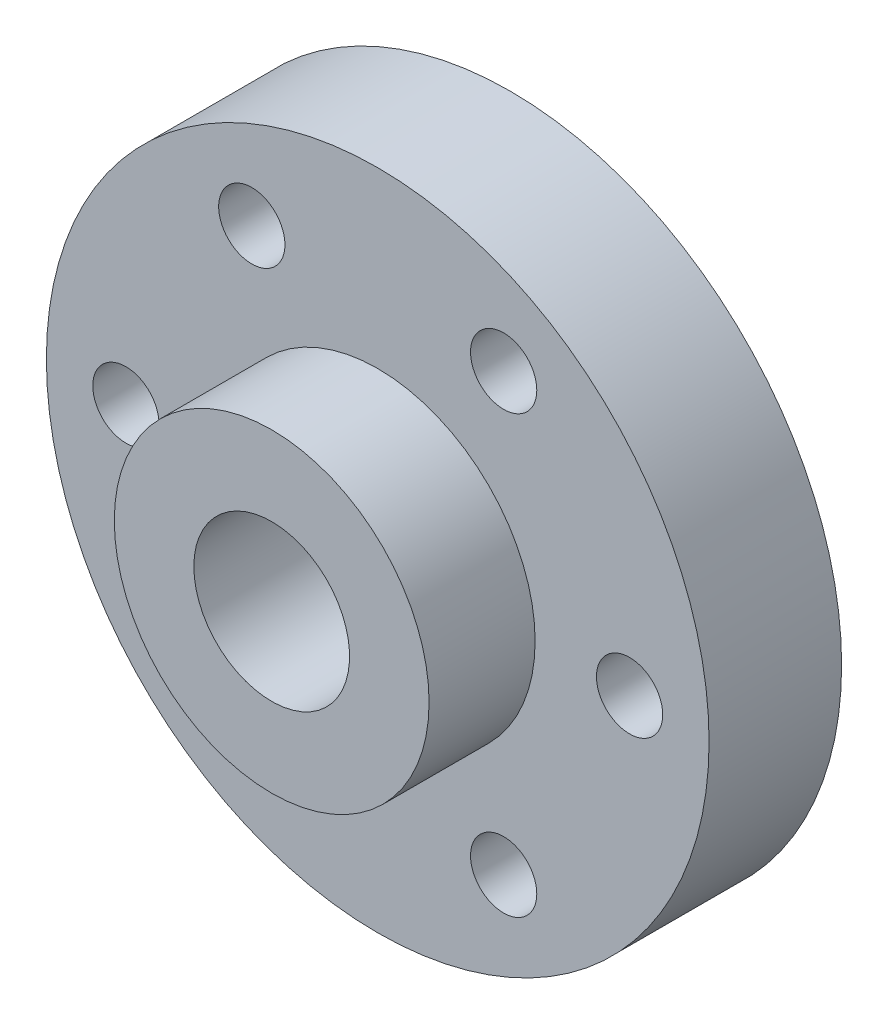
SolidWorks part; units mm, degrees
ref_plane "Front Plane" through (0, 0, 0) normal (0, 0, 1) x (1, 0, 0)
ref_plane "Top Plane" through (0, 0, 0) normal (0, 1, 0) x (1, 0, 0)
ref_plane "Right Plane" through (0, 0, 0) normal (1, 0, 0) x (0, 0, -1)
sketch "Sketch1" plane through (0, 0, 0) normal (0, 0, 1) x (1, 0, 0)
  circle A0 centre (0, 0) radius 12.7
  dimension "D1" = 25.4
extrude "Boss-Extrude1" add sketch "Sketch1" along normal blind 5.08
sketch "Sketch2" plane through (0, 0, 5.08) normal (0, 0, 1) x (1, 0, 0)
  circle A0 centre (0, 0) radius 6.0325
  dimension "D1" = 12.065
extrude "Boss-Extrude2" add sketch "Sketch2" along normal blind 4.064
sketch "Sketch3" plane through (0, 0, 0) normal (0, 0, -1) x (-1, 0, 0)
  circle A0 centre (0, 0) radius 2.9845
  dimension "D1" = 5.969
extrude "Cut-Extrude1" cut sketch "Sketch3" against normal through all
sketch "Sketch4" plane through (0, 0, 0) normal (0, 0, -1) x (-1, 0, 0)
  circle A0 centre (0, 0) radius 9.652 construction
  circle A1 centre (9.652, 0) radius 1.27
  point P3 (9.652, 0)
  dimension "D1" = 19.304
  dimension "D2" = 2.54
extrude "Cut-Extrude2" cut sketch "Sketch4" against normal through all
ref_axis "Axis1" through (0, 0, 9.144) along (0, 0, -1)
pattern_circular "CirPattern1" count 6 over 360 about axis through (0, 0, 9.144) along (0, 0, -1) of "Cut-Extrude2"
